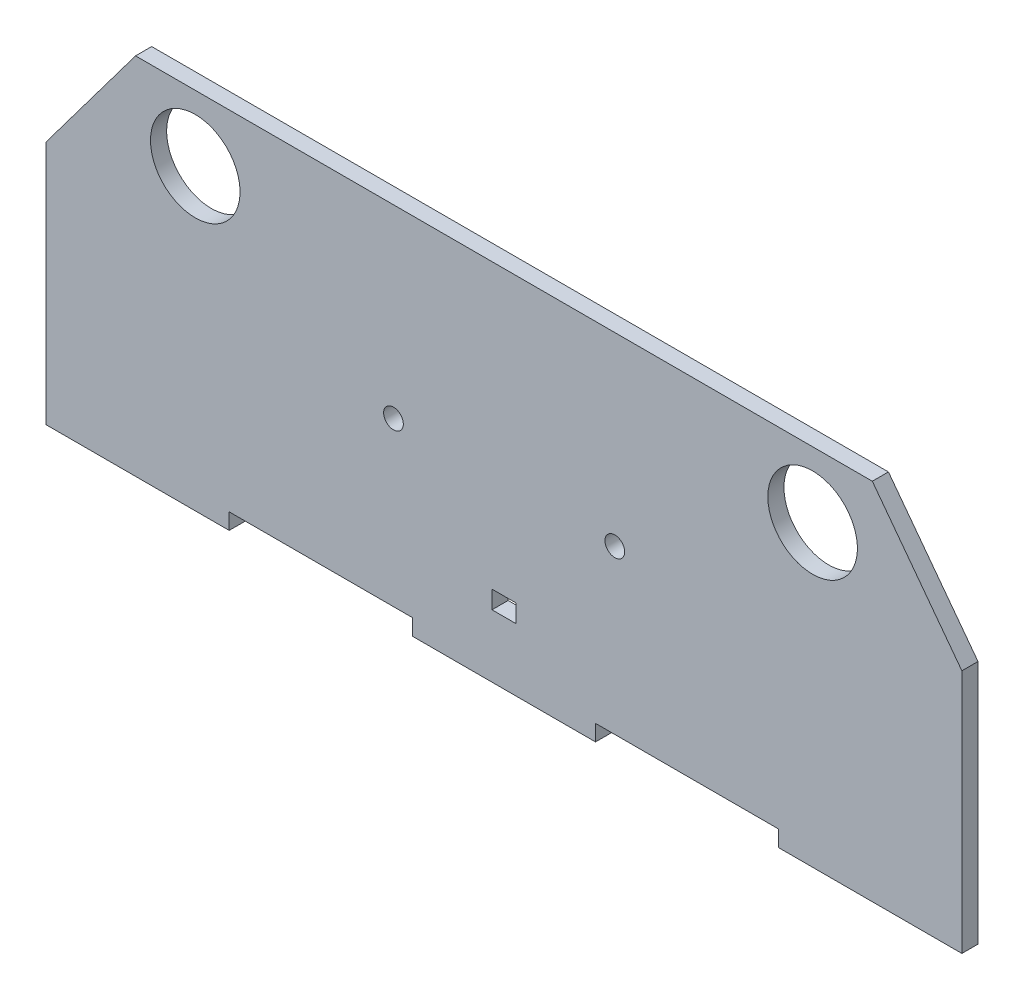
SolidWorks part; units mm, degrees
ref_plane "Ön Düzlem" through (0, 0, 0) normal (0, 0, 1) x (1, 0, 0)
ref_plane "Üst Düzlem" through (0, 0, 0) normal (0, 1, 0) x (1, 0, 0)
ref_plane "Sağ Düzlem" through (0, 0, 0) normal (1, 0, 0) x (0, 0, -1)
sketch "Sketch1" plane through (0, 0, 0) normal (0, 0, 1) x (1, 0, 0)
  line L7 (-61.7, 33) -> (61.7, 33)
  line L9 (-2, -17.5) -> (-2, -14.5)
  line L10 (-2, -14.5) -> (2, -14.5)
  line L11 (2, -14.5) -> (2, -17.5)
  line L12 (2, -17.5) -> (-2, -17.5)
  line L14 (-76.7, 13) -> (-61.7, 33)
  line L15 (61.7, 33) -> (76.7, 13)
  line L21 (-46.02, -28) -> (-46.02, -25.3)
  line L22 (-15.34, -28) -> (-15.34, -25.3)
  line L23 (15.34, -28) -> (15.34, -25.3)
  line L24 (46.02, -28) -> (46.02, -25.3)
  line L26 (-76.7, -23) -> (-76.7, 13)
  line L27 (-76.7, -23) -> (-76.7, -25.3)
  line L28 (76.7, -23) -> (76.7, 13)
  line L30 (76.7, -25.3) -> (76.7, -23)
  line L33 (-46.02, -28) -> (-76.7, -28)
  line L34 (-76.7, -28) -> (-76.7, -25.3)
  line L35 (-15.34, -25.3) -> (-46.02, -25.3)
  line L36 (-15.34, -28) -> (15.34, -28)
  line L37 (15.34, -25.3) -> (46.02, -25.3)
  line L38 (46.02, -28) -> (76.7, -28)
  line L39 (76.7, -28) -> (76.7, -25.3)
  circle A1 centre (-18.5, 2) radius 1.65
  circle A2 centre (18.5679, 2) radius 1.65
  circle A3 centre (-51.7, 22) radius 7.5
  circle A4 centre (51.7, 22) radius 7.5
  point P0 (0, 0)
  point P6 (76.7, 33)
  point P7 (-76.7, 33)
  dimension "D3" = 15
  dimension "D4" = 20
  dimension "D5" = 15
  dimension "D6" = 20
extrude "Boss-Extrude3" add sketch "Sketch1" along normal blind 2.7
